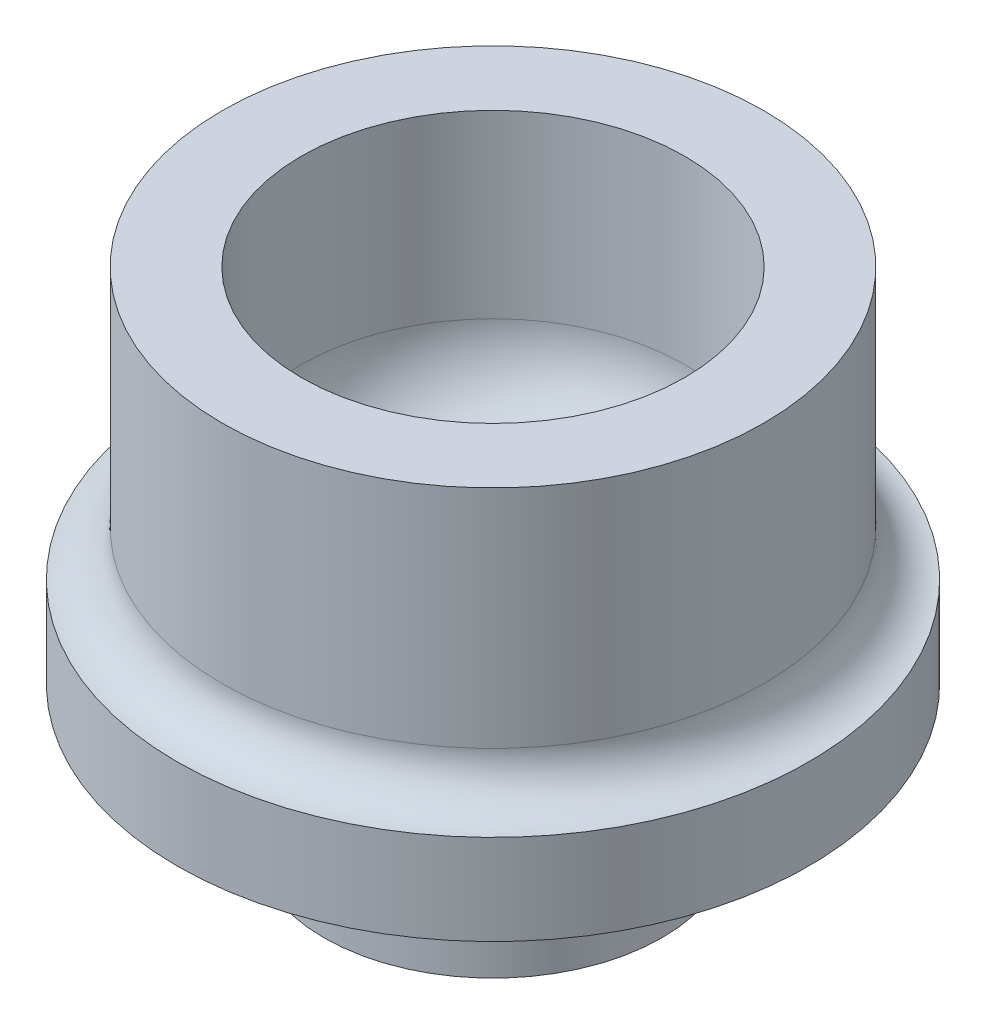
SolidWorks part; units mm, degrees
ref_plane "Alzado" through (0, 0, 0) normal (0, 0, 1) x (1, 0, 0)
ref_plane "Planta" through (0, 0, 0) normal (0, 1, 0) x (1, 0, 0)
ref_plane "Vista lateral" through (0, 0, 0) normal (1, 0, 0) x (0, 0, -1)
sketch "Croquis1" plane through (0, 0, 0) normal (0, 1, 0) x (1, 0, 0)
  circle A0 centre (0, 0) radius 7
  dimension "D1" = 14
extrude "Saliente-Extruir1" add sketch "Croquis1" along normal blind 2 contours A0 region at (0, 0, 0)
sketch "Croquis2" plane through (0, 2, 0) normal (0, 1, 0) x (1, 0, 0)
  circle A0 centre (0, 0) radius 4.25
  circle A1 centre (0, 0) radius 6
  dimension "D1" = 8.5
  dimension "D2" = 12
extrude "Saliente-Extruir2" add sketch "Croquis2" along normal blind 6
fillet "Redondeo3" radius 2 1 edges at (0, 2, 4.25)
fillet "Redondeo4" radius 1 1 edges at (0, 2, 6)
sketch "Croquis3" plane through (0, 0, 0) normal (0, -1, 0) x (1, 0, 0)
  circle A0 centre (0, 0) radius 3.75
  circle A1 centre (0, 0) radius 3.25
  dimension "D1" = 7.5
  dimension "D2" = 6.5
extrude "Saliente-Extruir3" add sketch "Croquis3" along normal blind 3
